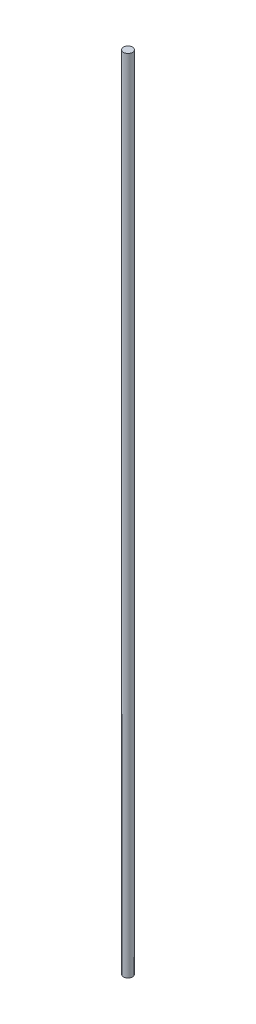
SolidWorks part; units mm, degrees
material "Thornel Mat VMA"
ref_plane "前视基准面" through (0, 0, 0) normal (0, 0, 1) x (1, 0, 0)
ref_plane "上视基准面" through (0, 0, 0) normal (0, 1, 0) x (1, 0, 0)
ref_plane "右视基准面" through (0, 0, 0) normal (1, 0, 0) x (0, 0, -1)
sketch "草图1" plane through (0, 0, 0) normal (0, 1, 0) x (1, 0, 0)
  circle A0 centre (0, 0) radius 1
  dimension "D1" = 2
extrude "凸台-拉伸1" add sketch "草图1" along normal blind 175
equation "\"m\"= 2"
